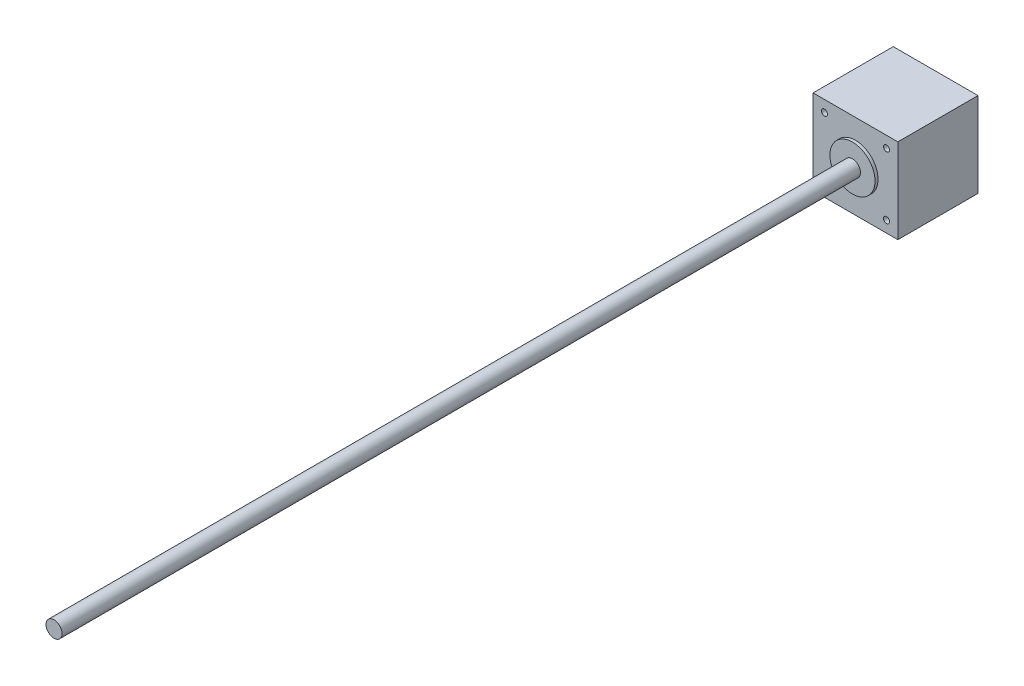
SolidWorks part; units mm, degrees
ref_plane "Front Plane" through (0, 0, 0) normal (0, 0, 1) x (1, 0, 0)
ref_plane "Top Plane" through (0, 0, 0) normal (0, 1, 0) x (1, 0, 0)
ref_plane "Right Plane" through (0, 0, 0) normal (1, 0, 0) x (0, 0, -1)
sketch "Sketch1" plane through (0, 0, 0) normal (0, 0, 1) x (1, 0, 0)
  line L1 (-21.15, -21.15) -> (21.15, -21.15)
  line L2 (-21.15, -21.15) -> (-21.15, 21.15)
  line L3 (-21.15, 21.15) -> (21.15, 21.15)
  line L4 (21.15, -21.15) -> (21.15, 21.15)
  line L5 (-21.15, -21.15) -> (21.15, 21.15) construction
  line L6 (-21.15, 21.15) -> (21.15, -21.15) construction
  circle A0 centre (15.5, 15.5) radius 1.5
  circle A1 centre (15.5, -15.5) radius 1.5
  circle A2 centre (-15.5, -15.5) radius 1.5
  circle A3 centre (-15.5, 15.5) radius 1.5
  circle A4 centre (0, 0) radius 11.25
  circle A5 centre (0, 0) radius 4
  point P0 (0, 0)
  point P17 (0, 0)
  dimension "D4" = 3
  dimension "D5" = 22.5
  dimension "D6" = 8
  dimension "D1" = 42.3
  dimension "D3" = 31
  dimension "D2" = 4
extrude "Boss-Extrude1" add sketch "Sketch1" against normal blind 40 contours L2 L3 L4 L1
extrude "Cut-Extrude1" cut sketch "Sketch1<3>" against normal blind 5 contours A2 | A0 | A1 | A3 region at (15.5, 15.5, 0) region at (15.5, -15.5, 0) region at (-15.5, -15.5, 0)
sketch "Sketch1<3>" plane through (0, 0, 0) normal (0, 0, 1) x (1, 0, 0) same geometry as "Sketch1"
extrude "Boss-Extrude2" add sketch "Sketch1<4>" along normal blind 1.5 contours A4 A5 region at (-10.9318, 0, 0)
sketch "Sketch1<4>" plane through (0, 0, 0) normal (0, 0, 1) x (1, 0, 0) same geometry as "Sketch1"
extrude "Boss-Extrude3" add sketch "Sketch1<5>" along normal blind 400 contours A5 region at (0, 0, 0)
sketch "Sketch1<5>" plane through (0, 0, 0) normal (0, 0, 1) x (1, 0, 0) same geometry as "Sketch1"
sketch "Sketch3" plane through (0, -21.15, 0) normal (0, -1, 0) x (1, 0, 0)
  line L0 (-21.15, -40) -> (21.15, -40) construction
  line L1 (-8.5, -40) -> (8.5, -40)
  line L2 (-8.5, -40) -> (-8.5, -31)
  line L3 (-8.5, -31) -> (8.5, -31)
  line L4 (8.5, -40) -> (8.5, -31)
  line L5 (0, 0) -> (0, -40) construction
  line L6 (-21.15, 0) -> (21.15, 0) construction
  dimension "D1" = 17
  dimension "D2" = 9
extrude "Boss-Extrude4" add sketch "Sketch3" along normal blind 5
equation "\"LeadScrewLength\"= 400"
equation "\"D1@Boss-Extrude3\"=\"LeadScrewLength\""
